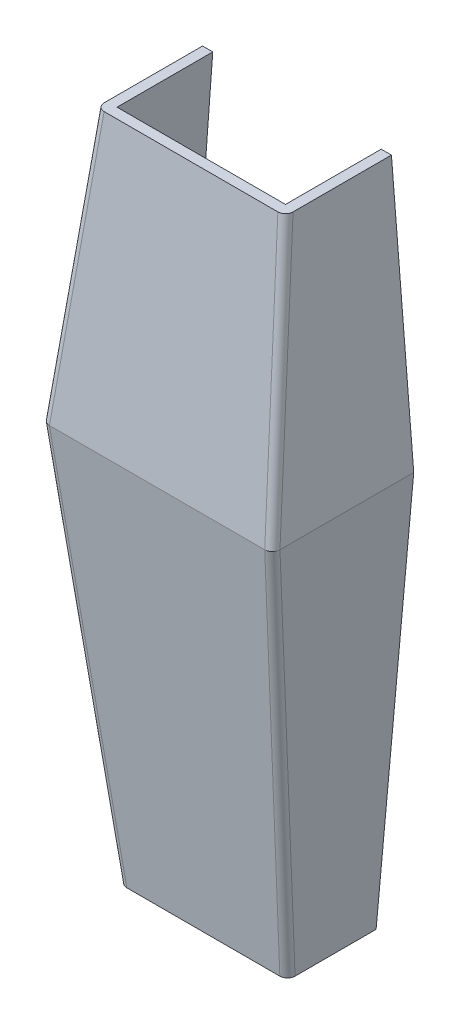
SolidWorks part; units mm, degrees
ref_plane "Front" through (0, 0, 0) normal (0, 0, 1) x (1, 0, 0)
ref_plane "Top" through (0, 0, 0) normal (0, 1, 0) x (1, 0, 0)
ref_plane "Right" through (0, 0, 0) normal (1, 0, 0) x (0, 0, -1)
sketch "Sketch2" plane through (0, 0, 0) normal (0, 1, 0) x (1, 0, 0)
  line L0 (0, -1.782) -> (0, 0) construction
  line L1 (-22.5973, -15.6441) -> (22.5973, -15.6441)
  line L2 (-22.5973, -15.6441) -> (-22.5973, 12.08)
  line L3 (-22.5973, 12.08) -> (22.5973, 12.08)
  line L4 (22.5973, -15.6441) -> (22.5973, 12.08)
  line L5 (-22.5973, -15.6441) -> (22.5973, 12.08) construction
  line L6 (-22.5973, 12.08) -> (22.5973, -15.6441) construction
  point P0 (0, -1.782)
ref_plane "Plane1" through (0, 52, 0) normal (0, 1, 0) x (1, 0, 0)
sketch "Sketch3" plane through (0, 52, 0) normal (0, 1, 0) x (1, 0, 0)
  line L0 (0, 1.3973) -> (0, 0) construction
  line L1 (-18.5189, -8.9942) -> (18.5189, -8.9942)
  line L2 (-18.5189, -8.9942) -> (-18.5189, 11.7888)
  line L3 (-18.5189, 11.7888) -> (18.5189, 11.7888)
  line L4 (18.5189, -8.9942) -> (18.5189, 11.7888)
  line L5 (-18.5189, -8.9942) -> (18.5189, 11.7888) construction
  line L6 (-18.5189, 11.7888) -> (18.5189, -8.9942) construction
  point P0 (0, 1.3973)
ref_plane "Plane2" through (0, -80, 0) normal (0, 1, 0) x (1, 0, 0)
sketch "Sketch4" plane through (0, -80, 0) normal (0, 1, 0) x (1, 0, 0)
  line L0 (0, 0) -> (0, 2.1203) construction
  line L1 (-16.4896, -6.5719) -> (16.4896, -6.5719)
  line L2 (-16.4896, -6.5719) -> (-16.4896, 10.8126)
  line L3 (-16.4896, 10.8126) -> (16.4896, 10.8126)
  line L4 (16.4896, -6.5719) -> (16.4896, 10.8126)
  line L5 (-16.4896, -6.5719) -> (16.4896, 10.8126) construction
  line L6 (-16.4896, 10.8126) -> (16.4896, -6.5719) construction
  point P0 (0, 2.1203)
sketch "Sketch7" plane through (0, 0, 0) normal (1, 0, 0) x (0, 0, -1)
  line L0 (10.8126, -80) -> (12.08, 0)
  line L1 (12.08, 0) -> (11.7888, 52)
  line L2 (-8.9942, 52) -> (-15.6441, 0)
  line L3 (-15.6441, 0) -> (-6.5719, -80)
sketch "Sketch8" plane through (0, 0, 0) normal (0, 0, 1) x (1, 0, 0)
  line L0 (-16.4896, -80) -> (-22.5973, 0)
  line L1 (-22.5973, 0) -> (-18.5189, 52)
  line L2 (16.4896, -80) -> (22.5973, 0)
  line L3 (22.5973, 0) -> (18.5189, 52)
ref_plane "Plane3" through (0, 0, 40) normal (0, 0, 1) x (1, 0, 0)
loft "Loft2" add profiles "Sketch3", "Sketch2" connector at (18.5189, 52, 8.9942) connector at (22.5973, 0, 15.6441)
loft "Loft3" add profiles "Sketch4", "Sketch2<3>" connector at (16.4896, -80, 6.5719) connector at (22.5973, 0, 15.6441)
sketch "Sketch2<3>" plane through (0, 0, 0) normal (0, 1, 0) x (1, 0, 0) same geometry as "Sketch2"
shell "Shell3" thickness 2 removed face at (0, 52, -1.3973) removed face at (10.2791, 39, -11.8616) removed face at (9.7717, -60, -11.1294) removed face at (0, -80, -2.1203)
fillet "Fillet1" radius 1.5 4 edges
ref_plane "Plane4" through (0, 0, 6.9779) normal (0, 0, 1) x (1, 0, 0)
sketch "Sketch11" plane through (0, 0, 6.9779) normal (0, 0, 1) x (1, 0, 0)
  line L1 (11.5, -22.0133) -> (-11.5, -22.0133)
  line L2 (11.5, -22.0133) -> (11.5, 22.0133)
  line L3 (11.5, 22.0133) -> (-11.5, 22.0133)
  line L4 (-11.5, -22.0133) -> (-11.5, 22.0133)
  line L5 (11.5, -22.0133) -> (-11.5, 22.0133) construction
  line L6 (11.5, 22.0133) -> (-11.5, -22.0133) construction
  line L7 (11.5, 60.574) -> (-11.5, 60.574) construction
  point P0 (0, 0)
